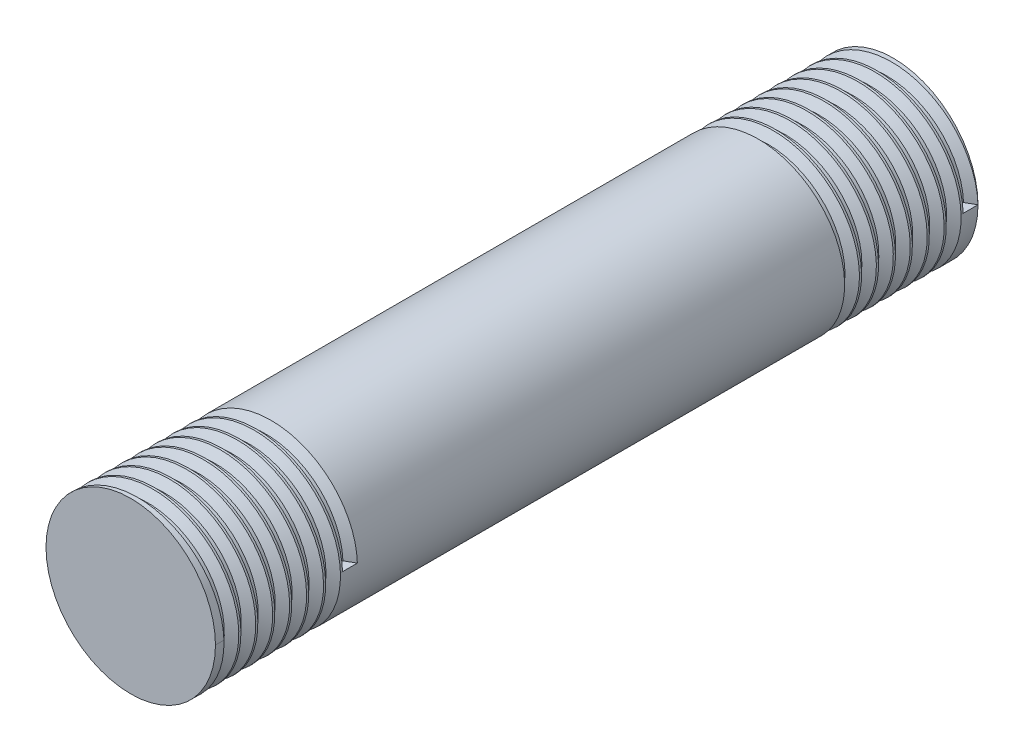
SolidWorks part; units mm, degrees
material "AISI 1020"
ref_plane "Front Plane" through (0, 0, 0) normal (0, 0, 1) x (1, 0, 0)
ref_plane "Top Plane" through (0, 0, 0) normal (0, 1, 0) x (1, 0, 0)
ref_plane "Right Plane" through (0, 0, 0) normal (1, 0, 0) x (0, 0, -1)
sketch "Sketch1" plane through (0, 0, 0) normal (0, 0, 1) x (1, 0, 0)
  circle A0 centre (0, 0) radius 10
extrude "Boss-Extrude1" add sketch "Sketch1" against normal blind 90
thread "Thread1" pitch 2 method cut profile "Thread Profile1" start angle 0, offset 0, length 15, pitch 2, diameter 20
ref_plane "Plane1" through (10, 0, -90) normal (0, -1, 0) x (1, 0, 0)
sketch "Thread Profile1" plane through (10, 0, -90) normal (0, -1, 0) x (1, 0, 0)
  line L0 (0, 0) -> (0, 2) construction
  line L11 (0, 0) -> (0, 1.75)
  line L12 (0, 1.75) -> (-1.0825, 1.125)
  line L13 (-1.0825, 1.125) -> (-1.0825, 0.625)
  line L15 (-1.0825, 0.625) -> (0, 0)
  line L17 (-1.0825, 0.875) -> (0, 0.875) construction
  point P2 (0, 0)
  dimension "Pitch" = 2
  dimension "Profile_Angle" = 60
  dimension "Profile_Land" = 0.5
  dimension "Profile_Height" = 1.0825
thread "Thread4" pitch 2 method cut profile "Thread Profile4" start angle 0, offset 0, length 15, pitch 2, diameter 20
ref_plane "Plane4" through (-10, 0, 0) normal (0, -1, 0) x (-1, 0, 0)
sketch "Thread Profile4" plane through (-10, 0, 0) normal (0, -1, 0) x (-1, 0, 0)
  line L0 (0, 0) -> (0, 2) construction
  line L11 (0, 0) -> (0, 1.75)
  line L12 (0, 1.75) -> (-1.0825, 1.125)
  line L13 (-1.0825, 1.125) -> (-1.0825, 0.625)
  line L15 (-1.0825, 0.625) -> (0, 0)
  line L17 (-1.0825, 0.875) -> (0, 0.875) construction
  point P2 (0, 0)
  dimension "Pitch" = 2
  dimension "Profile_Angle" = 60
  dimension "Profile_Land" = 0.5
  dimension "Profile_Height" = 1.0825
